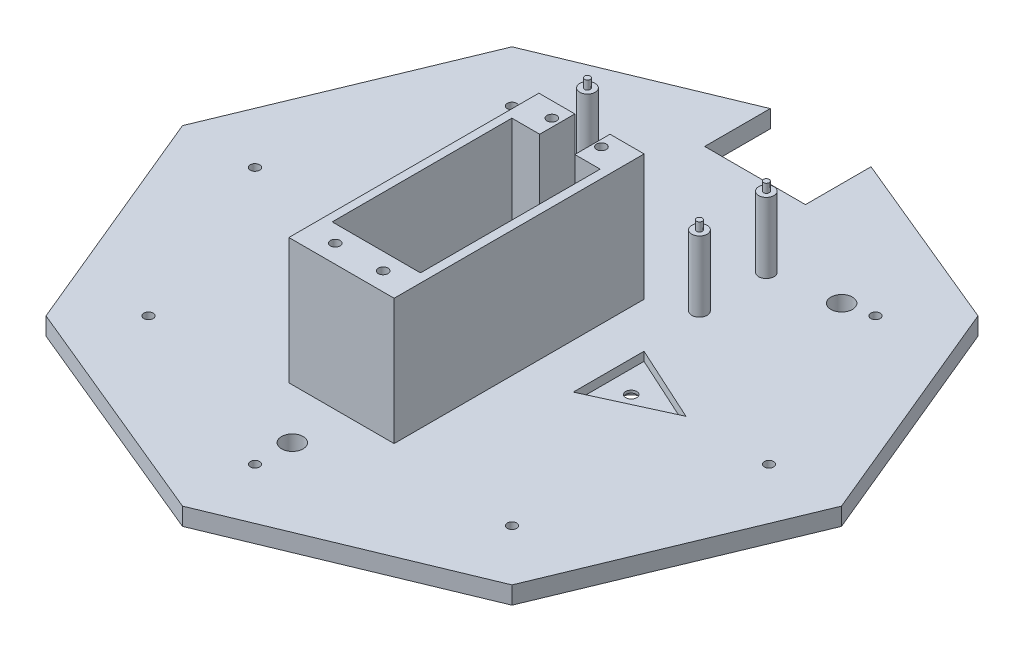
SolidWorks part; units mm, degrees
ref_plane "Ebene vorne" through (0, 0, 0) normal (0, 0, 1) x (1, 0, 0)
ref_plane "Ebene oben" through (0, 0, 0) normal (0, 1, 0) x (1, 0, 0)
ref_plane "Ebene rechts" through (0, 0, 0) normal (1, 0, 0) x (0, 0, -1)
sketch "Skizze2" plane through (0, 0, 0) normal (0, 1, 0) x (1, 0, 0)
  line L0 (-75, 0) -> (75, 0) construction
  line L1 (-55, 0) -> (55, 0) construction
  line L2 (0, -17.9575) -> (0, 17.9575) construction
  line L3 (-53.033, -53.033) -> (53.033, 53.033)
  line L4 (53.033, -53.033) -> (-53.033, 53.033)
  line L5 (-75, 0) -> (-53.033, 53.033)
  line L6 (-53.033, 53.033) -> (0, 75)
  line L7 (0, 75) -> (53.033, 53.033)
  line L8 (75, 0) -> (53.033, 53.033)
  line L9 (75, 0) -> (53.033, -53.033)
  line L10 (53.033, -53.033) -> (0, -75)
  line L11 (0, -75) -> (-53.033, -53.033)
  line L12 (-75, 0) -> (-53.033, -53.033)
  point P10 (0, 0)
  point P13 (0, 0)
  dimension "D1" = 150
  dimension "D2" = 75
  dimension "D3" = 150
  dimension "D4" = 150
  dimension "D5" = 45
  dimension "D6" = 45
  dimension "D7" = 75
  dimension "D8" = 75
extrude "Aufsatz-Linear austragen1" add sketch "Skizze2" along normal blind 3 and the other way blind 1 contours L7 L6 L4 L3 | L3 L0 L8 | L0 L4 L9 | L11 L10 L4 L3 | L5 L0 L4 | L0 L12 L3 region at (-42.6777, 0, -17.6777) region at (-42.6777, 0, 17.6777) region at (42.6777, 0, -17.6777) region at (0, 0, 42.6777) region at (0, 0, -42.6777) region at (42.6777, 0, 17.6777)
sketch "Skizze5" plane through (0, 0, 0) normal (0, 1, 0) x (1, 0, 0)
  line L5 (53.033, -53.033) -> (-53.033, -53.033) construction
  line L6 (-53.033, 53.033) -> (53.033, 53.033) construction
  line L17 (-4, 18.307) -> (-4, 10.307)
  line L18 (-12.1859, -38.593) -> (11.7641, -38.593)
  line L19 (-12.1859, -38.593) -> (-12.1859, 18.307)
  line L20 (-12.1859, 18.307) -> (-4, 18.307)
  line L21 (11.7641, -38.593) -> (11.7641, 18.307)
  line L24 (-10.3359, -30.593) -> (9.7641, -30.593)
  line L25 (-10.3359, -30.593) -> (-10.3359, 10.307)
  line L26 (-10.3359, 10.307) -> (-4, 10.307)
  line L27 (9.7641, -30.593) -> (9.7641, 10.307)
  line L31 (4, 10.307) -> (4, 18.307)
  line L32 (0, -17.9575) -> (0, 17.9575) construction
  line L33 (4, 18.307) -> (11.7641, 18.307)
  line L34 (4, 10.307) -> (9.7641, 10.307)
  dimension "D2" = 8
  dimension "D3" = 14.44
  dimension "D4" = 106.066
  dimension "D7" = 20.1
  dimension "D8" = 40.9
  dimension "D9" = 2
  dimension "D10" = 8
  dimension "D11" = 4
  dimension "D12" = 4
extrude "Aufsatz-Linear austragen3" add sketch "Skizze5" along normal blind 31.65
sketch "Skizze7" plane through (0, 3, 0) normal (0, 1, 0) x (1, 0, 0)
  line L0 (-17.9575, 0) -> (17.9575, 0) construction
  line L5 (-35, -40) -> (33.401, 38.1726) construction
  line L6 (-33.3537, 38.1186) -> (35, -40) construction
  circle A0 centre (35.0329, 40) radius 2.45
  circle A1 centre (-34.9671, 39.9624) radius 2.45
  circle A2 centre (0, -50) radius 2.45
  point P0 (0, 0)
  dimension "D3" = 4.9
  dimension "D4" = 4.9
  dimension "D5" = 4.9
  dimension "D6" = 50
  dimension "D1" = 80
  dimension "D2" = 70
extrude "Schnitt-Linear austragen2" cut sketch "Skizze7" against normal through all
sketch "Skizze8" plane through (0, 3, 0) normal (0, 1, 0) x (1, 0, 0)
  line L0 (-75, 0) -> (75, 0) construction
  line L7 (-22, 8.05) -> (-22, -8.05)
  line L8 (-40.3423, -0.3395) -> (-22, -8.05) construction
  line L9 (-40.3423, 0.3395) -> (-22, 8.05) construction
  line L12 (22, 8.05) -> (22, -8.05)
  line L15 (22, 8.05) -> (36.597, 1.9139) construction
  line L16 (22, -8.05) -> (40.3423, -0.3395) construction
  line L18 (0, -17.9575) -> (0, 17.9575) construction
  line L19 (-39.6, 0) -> (-22, -8.05)
  line L21 (-22, 8.05) -> (-39.6, 0)
  line L22 (22, -8.05) -> (39.6, 0)
  line L23 (39.6, 0) -> (22, 8.05)
  line L24 (22, -8.05) -> (22, 8.05)
  point P2 (-41.15, 0)
  point P7 (41.15, 0)
  dimension "D1" = 22
  dimension "D2" = 22
  dimension "D3" = 16.1
  dimension "D4" = 17.6
  dimension "D5" = 17.6
  dimension "D6" = 16.1
extrude "Schnitt-Linear austragen6" cut sketch "Skizze8" against normal blind 2 contours L7 L21 L19 | L22 L23 L12 region at (-27.8667, 3, 0) region at (27.8667, 3, 0)
sketch "Skizze10" plane through (0, 1, 0) normal (0, 1, 0) x (1, 0, 0)
  line L0 (22, 8.05) -> (22, -8.05) construction
  line L1 (-17.9575, 0) -> (17.9575, 0) construction
  line L2 (-22, 8.05) -> (-22, -8.05) construction
  line L7 (41.9977, 0.05) -> (22.7023, 0.05) construction
  circle A0 centre (-27.0878, 0) radius 1.25
  circle A1 centre (27.09, 0.05) radius 1.25
  dimension "D1" = 2.5
  dimension "D2" = 0
  dimension "D3" = 0
  dimension "D4" = 5.09
  dimension "D5" = 5.0878
extrude "Schnitt-Linear austragen7" cut sketch "Skizze10" against normal through all
sketch "Skizze11" plane through (0, -1, 0) normal (0, -1, 0) x (1, 0, 0)
  circle A0 centre (-27.0878, 0) radius 2.75
  circle A1 centre (27.09, -0.05) radius 2.75
  dimension "D1" = 5.5
  dimension "D2" = 5.5
extrude "Schnitt-Linear austragen8" cut sketch "Skizze11" against normal blind 1.4
sketch "Skizze14" plane through (0, 3, 0) normal (0, 1, 0) x (1, 0, 0)
  line L0 (0, 0) -> (-51.0988, 51.0988) construction
  line L1 (-51.0988, 51.0988) -> (0, 0) construction
  line L2 (0, 0) -> (44.6211, 44.6211) construction
  line L3 (44.6211, 44.6211) -> (0, 0) construction
  line L4 (0, 0) -> (42.9287, -42.9287) construction
  line L5 (42.9287, -42.9287) -> (0, 0) construction
  line L6 (0, 0) -> (-43.4336, -43.4336) construction
  circle A1 centre (-58.5, 0) radius 1.075
  circle A3 centre (-41.3657, 41.3657) radius 1.075
  circle A4 centre (41.3657, 41.3657) radius 1.075
  circle A5 centre (58.5, 0) radius 1.075
  circle A6 centre (41.3657, -41.3657) radius 1.075
  circle A7 centre (-41.3657, -41.3657) radius 1.075
  circle A8 centre (0, -58.5) radius 1.075
  dimension "D2" = 2.15
  dimension "D3" = 2.15
  dimension "D4" = 2.15
  dimension "D5" = 2.15
  dimension "D6" = 2.15
  dimension "D7" = 2.15
  dimension "D8" = 2.15
extrude "Schnitt-Linear austragen9" cut sketch "Skizze14" against normal blind 10
sketch "Skizze15" plane through (0, 3, 0) normal (0, 1, 0) x (1, 0, 0)
  line L0 (0, -17.9575) -> (0, 17.9575) construction
  line L1 (-20.36, 22.307) -> (20.36, 22.307)
  line L2 (-20.36, 22.307) -> (-20.36, 37.537)
  line L3 (-20.36, 37.537) -> (20.36, 37.537)
  line L4 (20.36, 22.307) -> (20.36, 37.537)
  line L5 (-20.36, 22.307) -> (20.36, 37.537) construction
  line L6 (-20.36, 37.537) -> (20.36, 22.307) construction
  line L7 (4, 18.307) -> (11.7641, 18.307) construction
  circle A0 centre (-20.36, 37.537) radius 1.75
  circle A1 centre (-20.36, 22.307) radius 1.75
  circle A2 centre (20.36, 22.307) radius 1.75
  circle A3 centre (20.36, 37.537) radius 1.75
  point P0 (0, 29.922)
  dimension "D4" = 3.5
  dimension "D5" = 3.5
  dimension "D6" = 3.5
  dimension "D7" = 3.5
  dimension "D1" = 40.72
  dimension "D2" = 15.23
  dimension "D3" = 4
extrude "Aufsatz-Linear austragen4" add sketch "Skizze15" along normal blind 16 contours L4 A3 L3 | L3 A3 L4 | L2 A1 L1 | L1 A1 L2 | L2 A0 L3 | L3 A0 L2 | A2 region at (-19.6173, 3, -23.0497) region at (-20.6076, 3, -22.0594) region at (-20.6076, 3, -37.7846) region at (-19.6173, 3, -36.7943) region at (19.6173, 3, -36.7943) region at (20.6076, 3, -37.7846)
sketch "Skizze16" plane through (0, 19, 0) normal (0, 1, 0) x (1, 0, 0)
  circle A0 centre (20.36, 22.307) radius 0.65
  circle A1 centre (20.36, 37.537) radius 0.65
  circle A2 centre (-20.36, 37.537) radius 0.65
  circle A3 centre (-20.36, 22.307) radius 0.65
  dimension "D1" = 1.3
  dimension "D2" = 1.3
  dimension "D3" = 1.3
  dimension "D4" = 1.3
extrude "Aufsatz-Linear austragen5" add sketch "Skizze16" along normal blind 2
sketch "Skizze18" plane through (0, 31.65, 0) normal (0, 1, 0) x (1, 0, 0)
  line L0 (4, 18.307) -> (4, 10.307) construction
  circle A0 centre (-5.7859, 14.857) radius 1.1
  circle A1 centre (5.5, 14.857) radius 1.1
  circle A2 centre (5.1141, -34.443) radius 1.1
  circle A3 centre (-5.7859, -34.443) radius 1.1
  dimension "D1" = 2.2
  dimension "D2" = 2.2
  dimension "D3" = 2.2
  dimension "D4" = 2.2
  dimension "D5" = 1.5
extrude "Schnitt-Linear austragen10" cut sketch "Skizze18" against normal blind 13
sketch "Skizze19" plane through (0, 3, 0) normal (0, 1, 0) x (1, 0, 0)
  line L0 (11.4686, 55.3238) -> (11.4686, 70.2496)
  line L1 (0, 75) -> (53.033, 53.033) construction
  line L2 (11.4686, 70.2496) -> (0, 75)
  line L3 (0, 75) -> (-11.4686, 70.2496)
  line L4 (-53.033, 53.033) -> (0, 75) construction
  line L5 (-11.4686, 70.2496) -> (-11.4686, 55.3238)
  line L6 (-11.4686, 55.3238) -> (11.4686, 55.3238)
extrude "Schnitt-Linear austragen11" cut sketch "Skizze19" against normal blind 10
